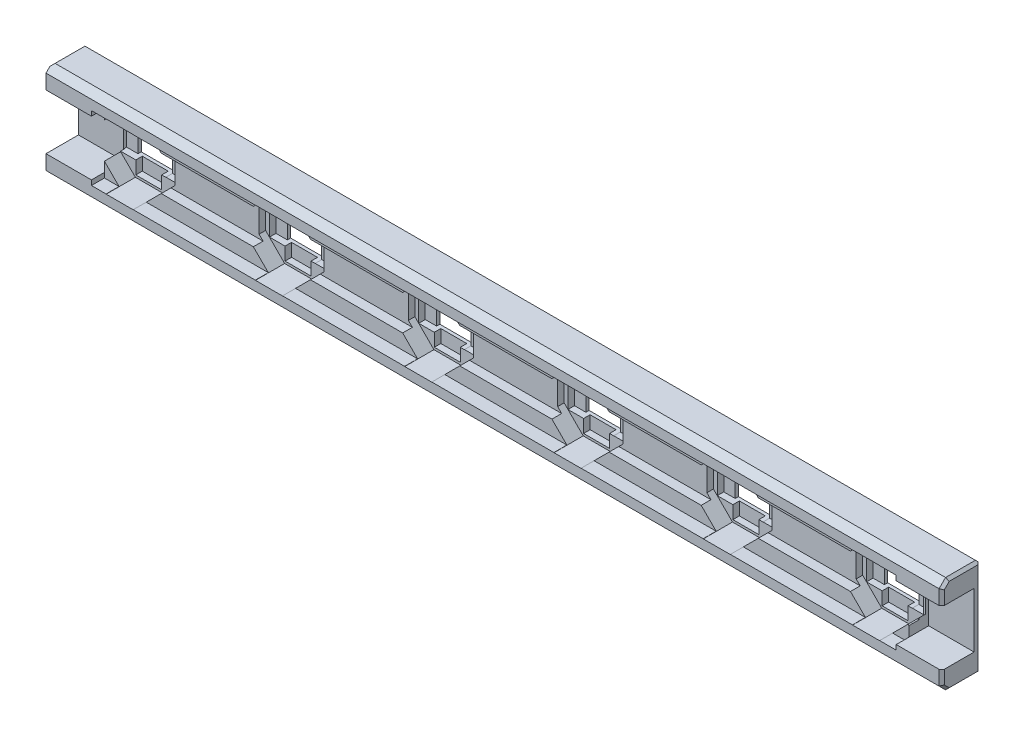
SolidWorks part; units mm, degrees
ref_plane "Front Plane" through (0, 0, 0) normal (0, 0, 1) x (1, 0, 0)
ref_plane "Top Plane" through (0, 0, 0) normal (0, 1, 0) x (1, 0, 0)
ref_plane "Right Plane" through (0, 0, 0) normal (1, 0, 0) x (0, 0, -1)
sketch "Sketch1" plane through (0, 0, 0) normal (0, 0, 1) x (1, 0, 0)
  line L1 (-91.75, 25.6543) -> (46.25, 25.6543)
  line L2 (-91.75, 25.6543) -> (-91.75, 10.6543)
  line L3 (-91.75, 10.6543) -> (46.25, 10.6543)
  line L4 (46.25, 25.6543) -> (46.25, 10.6543)
  dimension "D1" = 138
  dimension "D2" = 15
extrude "Boss-Extrude1" add sketch "Sketch1" along normal blind 6
sketch "Sketch12" plane through (46.25, 0, 0) normal (1, 0, 0) x (0, 0, -1)
  line L0 (-6, 25.6543) -> (-6, 24.6543)
  line L1 (-6, 10.6543) -> (-6, 25.6543) construction
  line L2 (-6, 24.6543) -> (-5, 25.6543)
  line L3 (-6, 25.6543) -> (0, 25.6543) construction
  line L4 (-5, 25.6543) -> (-6, 25.6543)
  line L5 (-6, 10.6543) -> (-5, 10.6543)
  line L6 (-6, 10.6543) -> (0, 10.6543) construction
  line L7 (-5, 10.6543) -> (-6, 11.6543)
  line L8 (-6, 10.6543) -> (-6, 25.6543) construction
  line L9 (-6, 11.6543) -> (-6, 10.6543)
  dimension "D1" = 1
  dimension "D2" = 1
  dimension "D3" = 1
extrude "Cut-Extrude8" cut sketch "Sketch12" against normal up to surface (138 mm away) up to face at (-91.75, 18.1543, 3)
sketch "Sketch13" plane through (0, 0, 0) normal (0, 0, -1) x (-1, 0, 0)
  line L0 (91.75, 25.6543) -> (91.75, 10.6543) construction
  line L1 (89.25, 23.1543) -> (89.75, 23.1543)
  line L2 (89.25, 23.1543) -> (89.25, 13.1543)
  line L3 (89.25, 13.1543) -> (89.75, 13.1543)
  line L4 (89.75, 23.1543) -> (89.75, 13.1543)
  line L5 (-46.25, 25.6543) -> (91.75, 25.6543) construction
  dimension "D1" = 2
  dimension "D2" = 0.5
  dimension "D3" = 10
  dimension "D4" = 2.5
extrude "Cut-Extrude9" cut sketch "Sketch13" against normal blind 0.6
fillet "Fillet1" radius 0.25 1 edges at (-89.75, 18.1543, 0)
fillet "Fillet2" radius 0.25 4 edges at (-89.5, 23.1543, 0.6) (-89.75, 18.1543, 0.6) (-89.5, 13.1543, 0.6) (-89.25, 18.1543, 0.6)
chamfer "Chamfer1" distance 0.4 angle 45 2 edges at (-22.75, 10.6543, 0) (-22.75, 25.6543, 0)
chamfer "Chamfer2" distance 0.4 angle 45 2 edges at (46.25, 18.1543, 0) (-91.75, 18.1543, 0)
chamfer "Chamfer3" distance 0.4 angle 45 2 edges at (-91.75, 10.6543, 2.7) (-91.75, 25.6543, 2.7)
chamfer "Chamfer5" distance 0.4 angle 45 5 edges at (46.25, 25.1543, 5.5) (46.25, 25.6543, 2.7) (46.25, 18.1543, 6) (46.25, 11.1543, 5.5) (46.25, 10.6543, 2.7)
sketch "Sketch15" plane through (0, 0, 6) normal (0, 0, 1) x (1, 0, 0)
  line L0 (-91.75, 24.6543) -> (-91.75, 11.6543) construction
  line L1 (-75.3821, 20.2328) -> (-78.3215, 23.1722)
  line L2 (-78.3215, 23.1722) -> (-82.4785, 23.1722)
  line L3 (-82.4785, 23.1722) -> (-85.4179, 20.2328)
  line L4 (-85.4179, 20.2328) -> (-85.4179, 16.0758)
  line L5 (-85.4179, 16.0758) -> (-82.4785, 13.1364)
  line L6 (-82.4785, 13.1364) -> (-78.3215, 13.1364)
  line L7 (-78.3215, 13.1364) -> (-75.3821, 16.0758)
  line L8 (-75.3821, 16.0758) -> (-75.3821, 20.2328)
  line L9 (-91.35, 25.6543) -> (45.85, 25.6543) construction
  line L10 (-91.75, 11.6543) -> (45.85, 11.6543) construction
  circle A0 centre (-80.4, 18.1543) radius 5.0179 construction
  dimension "D1" = 11.35
  dimension "D2" = 7.5
extrude "Cut-Extrude10" cut sketch "Sketch15" against normal blind 4.5
sketch "Sketch16" plane through (0, 0, 1.5) normal (0, 0, 1) x (1, 0, 0)
  line L1 (-83.0679, 20.7864) -> (-77.7679, 20.7864)
  line L2 (-83.0679, 20.7864) -> (-83.0679, 15.4864)
  line L3 (-83.0679, 15.4864) -> (-77.7679, 15.4864)
  line L4 (-77.7679, 20.7864) -> (-77.7679, 15.4864)
  line L5 (-85.4179, 20.2328) -> (-85.4179, 16.0758) construction
  line L6 (-82.4785, 13.1364) -> (-78.3215, 13.1364) construction
  point P4 (-83.0679, 18.1364)
  point P7 (-85.4179, 18.1543)
  point P10 (-80.4, 13.1364)
  point P11 (-80.4179, 15.4864)
  dimension "D1" = 5.3
  dimension "D2" = 5.3
  dimension "D3" = 2.35
  dimension "D4" = 2.35
extrude "Cut-Extrude11" cut sketch "Sketch16" against normal blind 4.5
sketch "Sketch17" plane through (0, 0, 1.5) normal (0, 0, 1) x (1, 0, 0)
  line L0 (-83.0679, 15.4864) -> (-77.7679, 15.4864) construction
  line L1 (-82.4179, 15.4864) -> (-78.4179, 15.4864)
  line L2 (-82.4179, 15.4864) -> (-82.4179, 13.4864)
  line L3 (-82.4179, 13.4864) -> (-78.4179, 13.4864)
  line L4 (-78.4179, 15.4864) -> (-78.4179, 13.4864)
  line L5 (-77.7679, 20.7864) -> (-83.0679, 20.7864) construction
  line L6 (-82.4179, 20.7864) -> (-78.4179, 20.7864)
  line L7 (-82.4179, 20.7864) -> (-82.4179, 22.7864)
  line L8 (-82.4179, 22.7864) -> (-78.4179, 22.7864)
  line L9 (-78.4179, 20.7864) -> (-78.4179, 22.7864)
  line L10 (-77.7679, 15.4864) -> (-77.7679, 20.7864) construction
  dimension "D1" = 4
  dimension "D2" = 4
  dimension "D3" = 2
  dimension "D4" = 2
  dimension "D5" = 0.65
  dimension "D6" = 0.65
extrude "Cut-Extrude12" cut sketch "Sketch17" against normal blind 1
sketch "Sketch18" plane through (0, 0, 1.5) normal (0, 0, 1) x (1, 0, 0)
  line L1 (-83.0679, 15.4864) -> (-84.8179, 15.4864)
  line L2 (-83.0679, 15.4864) -> (-83.0679, 20.8045)
  line L3 (-83.0679, 20.8045) -> (-84.8179, 20.8045)
  line L4 (-84.8179, 15.4864) -> (-84.8179, 20.8045)
  line L5 (-77.7679, 20.7864) -> (-76.0179, 20.7864)
  line L6 (-77.7679, 20.7864) -> (-77.7679, 15.5045)
  line L7 (-77.7679, 15.5045) -> (-76.0179, 15.5045)
  line L8 (-76.0179, 20.7864) -> (-76.0179, 15.5045)
  dimension "D1" = 1.75
  dimension "D2" = 1.75
extrude "Cut-Extrude13" cut sketch "Sketch18" against normal blind 1
pattern_linear "LPattern1" count 6 spacing 23 along (1, 0, 0) of "Cut-Extrude10", "Cut-Extrude11", "Cut-Extrude12", "Cut-Extrude13"
sketch "Sketch19" plane through (0, 0, 6) normal (0, 0, 1) x (1, 0, 0)
  line L0 (-91.75, 24.6543) -> (-91.75, 11.6543) construction
  line L1 (-91.75, 22.4043) -> (-84.75, 22.4043)
  line L2 (-91.75, 22.4043) -> (-91.75, 13.9043)
  line L3 (-91.75, 13.9043) -> (-84.75, 13.9043)
  line L4 (-84.75, 22.4043) -> (-84.75, 13.9043)
  line L6 (-91.35, 10.6543) -> (45.85, 10.6543) construction
  line L14 (46.25, 24.4886) -> (46.25, 11.82) construction
  line L15 (46.25, 22.4043) -> (39.25, 22.4043)
  line L16 (46.25, 22.4043) -> (46.25, 13.9043)
  line L17 (46.25, 13.9043) -> (39.25, 13.9043)
  line L18 (39.25, 22.4043) -> (39.25, 13.9043)
  dimension "D1" = 8.5
  dimension "D2" = 3.25
  dimension "D3" = 7
  dimension "D4" = 8.5
  dimension "D5" = 7
  dimension "D6" = 3.25
extrude "Cut-Extrude14" cut sketch "Sketch19" against normal blind 5
sketch "Sketch20" plane through (0, 0, 6) normal (0, 0, 1) x (1, 0, 0)
  line L0 (-91.35, 10.6543) -> (45.85, 10.6543) construction
  line L1 (39.25, 13.1543) -> (-84.75, 13.1543)
  line L2 (39.25, 13.1543) -> (39.25, 23.1543)
  line L3 (39.25, 23.1543) -> (-84.75, 23.1543)
  line L4 (-84.75, 13.1543) -> (-84.75, 23.1543)
  line L6 (-84.75, 20.9007) -> (-84.75, 22.4043) construction
  dimension "D1" = 10
  dimension "D2" = 2.5
  dimension "D3" = 0
extrude "Cut-Extrude15" cut sketch "Sketch20" against normal blind 2
sketch "Sketch21" plane through (-16.4179, 0, 0) normal (1, 0, 0) x (0, 0, -1)
  line L0 (-4, 20.6007) -> (-4, 22.4043) construction
  line L3 (-4, 20.8507) -> (-2.5, 20.8507)
  line L4 (-4, 20.8507) -> (-4, 15.4579)
  line L5 (-4, 15.4579) -> (-2.5, 15.4579)
  line L6 (-2.5, 20.8507) -> (-2.5, 15.4579)
  line L7 (-1.5, 20.6007) -> (-4, 20.6007) construction
  line L8 (-4, 15.7079) -> (-1.5, 15.7079) construction
  dimension "D8" = 0.25
  dimension "D9" = 0.25
  dimension "D10" = 1.5
extrude "Cut-Extrude16" cut sketch "Sketch21" against normal through all both and the other way through all
